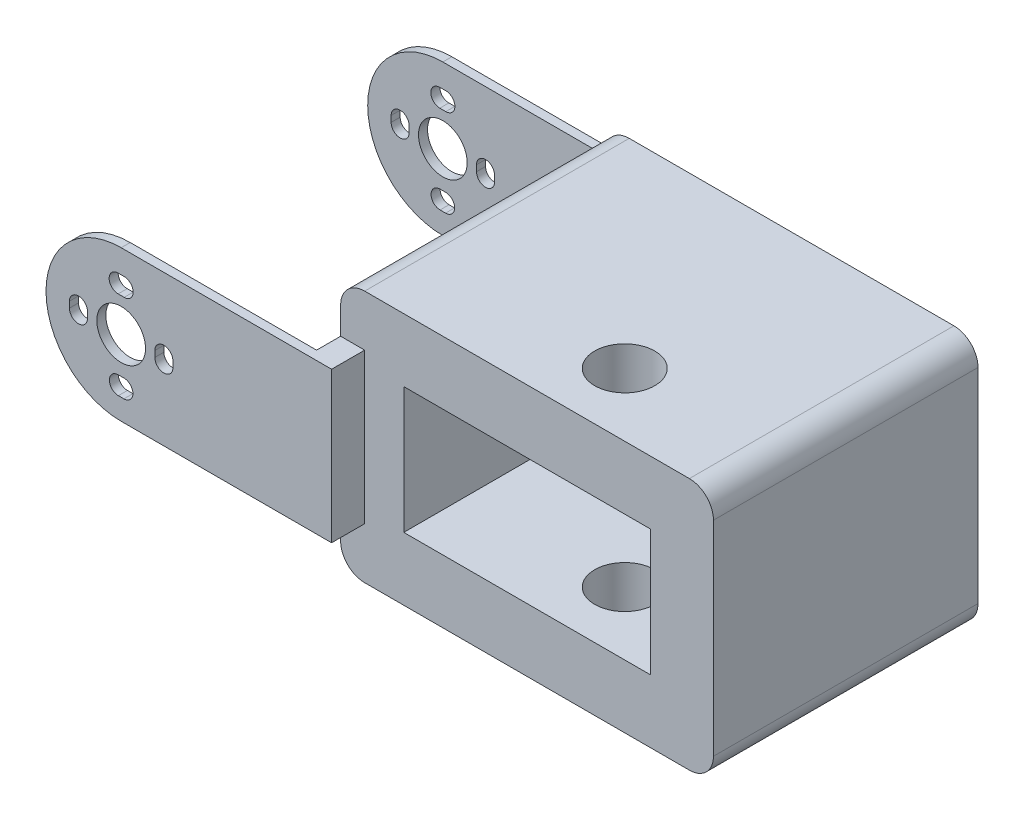
SolidWorks part; units mm, degrees
note: The reader was unsure of these and kept them because the rebuilt part matched: shared geometry of "Sketch3<8>", "Sketch3<11>", "草圖2<3>".
ref_plane "前基準面" through (0, 0, 0) normal (0, 0, 1) x (1, 0, 0)
ref_plane "上基準面" through (0, 0, 0) normal (0, 1, 0) x (1, 0, 0)
ref_plane "右基準面" through (0, 0, 0) normal (1, 0, 0) x (0, 0, -1)
sketch "Sketch1" plane through (0, 0, 0) normal (0, 0, 1) x (1, 0, 0)
  line L0 (-29.0958, -4.1361) -> (32.9042, -4.1361) construction
  line L1 (-18.5958, 6.3639) -> (22.4042, 6.3639)
  line L2 (-18.5958, 6.3639) -> (-18.5958, -14.6361)
  line L3 (-18.5958, -14.6361) -> (22.4042, -14.6361)
  line L4 (22.4042, 6.3639) -> (22.4042, -14.6361)
  line L5 (-29.0958, 16.8639) -> (32.9042, 16.8639)
  line L6 (-29.0958, 16.8639) -> (-29.0958, -25.1361)
  line L7 (-29.0958, -25.1361) -> (32.9042, -25.1361)
  line L8 (32.9042, 16.8639) -> (32.9042, -25.1361)
  line L9 (1.9042, 16.8639) -> (1.9042, -25.1361) construction
  line L10 (22.4042, -4.1361) -> (-18.5958, -4.1361) construction
  line L11 (1.9042, 6.3639) -> (1.9042, -14.6361) construction
  point P16 (1.9042, -4.1361)
  point P17 (1.9042, -4.1361)
  dimension "D1" = 21
  dimension "D2" = 41
  dimension "D3" = 62
  dimension "D4" = 42
extrude "Boss-Extrude1" add sketch "Sketch1" along normal blind 43
sketch "Sketch2" plane through (0, 0, 43) normal (0, 0, 1) x (1, 0, 0)
  line L0 (-18.5958, -4.1361) -> (-29.0958, -4.1361) construction
  line L1 (-25.0958, -4.1361) -> (-29.0958, -4.1361) construction
  line L3 (-29.0958, 16.8639) -> (-29.0958, -25.1361) construction
  line L4 (-18.5958, 6.3639) -> (-18.5958, -14.6361) construction
  line L5 (-29.0958, 8.3639) -> (-25.0958, 8.3639)
  line L6 (-29.0958, 8.3639) -> (-29.0958, -16.6361)
  line L7 (-29.0958, -16.6361) -> (-25.0958, -16.6361)
  line L8 (-25.0958, 8.3639) -> (-25.0958, -16.6361)
  dimension "D1" = 25
  dimension "D2" = 4
extrude "Boss-Extrude2" add sketch "Sketch2" along normal blind 4
sketch "Sketch3" plane through (0, 0, 47) normal (0, 0, 1) x (1, 0, 0)
  line L0 (-60.5958, 2.9639) -> (-59.5958, 2.9639) construction
  line L1 (-25.0958, 8.3639) -> (-60.0958, 8.3639)
  line L2 (-25.0958, 8.3639) -> (-25.0958, -16.6361)
  line L3 (-25.0958, -16.6361) -> (-60.0958, -16.6361)
  line L4 (-60.0958, 8.3639) -> (-60.0958, -16.6361)
  line L5 (-60.5958, 4.4639) -> (-59.5958, 4.4639)
  line L6 (-60.5958, 1.4639) -> (-59.5958, 1.4639)
  line L7 (-60.0958, 8.3639) -> (-60.0958, -16.6361) construction
  line L8 (-60.5559, -11.6762) -> (-59.6357, -11.6762) construction
  line L9 (-60.5559, -10.1762) -> (-59.6357, -10.1762)
  line L10 (-60.5559, -13.1762) -> (-59.6357, -13.1762)
  line L11 (-60.0958, -4.1361) -> (-72.5958, -4.1361) construction
  line L12 (-67.1958, -3.6361) -> (-67.1958, -4.6361) construction
  line L15 (-65.6958, -3.6361) -> (-65.6958, -4.6361)
  line L16 (-68.6958, -3.6361) -> (-68.6958, -4.6361)
  line L17 (-52.9958, -3.6361) -> (-52.9958, -4.6361) construction
  line L18 (-51.4958, -3.6361) -> (-51.4958, -4.6361)
  line L19 (-54.4958, -3.6361) -> (-54.4958, -4.6361)
  line L20 (-60.0958, -4.1361) -> (-25.0958, -4.1361) construction
  line L21 (-29.0958, 8.3639) -> (-29.0958, -16.6361) construction
  arc A0 (-60.0958, 8.3639) -> (-60.0958, -16.6361) centre (-60.0958, -4.1361) ccw
  circle A1 centre (-60.0958, -4.1361) radius 4.05
  arc A3 (-60.5958, 4.4639) -> (-60.5958, 1.4639) centre (-60.5958, 2.9639) ccw
  arc A4 (-59.5958, 1.4639) -> (-59.5958, 4.4639) centre (-59.5958, 2.9639) ccw
  arc A5 (-60.5559, -10.1762) -> (-60.5559, -13.1762) centre (-60.5559, -11.6762) ccw
  arc A6 (-59.6357, -13.1762) -> (-59.6357, -10.1762) centre (-59.6357, -11.6762) ccw
  arc A9 (-65.6958, -3.6361) -> (-68.6958, -3.6361) centre (-67.1958, -3.6361) ccw
  arc A10 (-68.6958, -4.6361) -> (-65.6958, -4.6361) centre (-67.1958, -4.6361) ccw
  arc A11 (-51.4958, -3.6361) -> (-54.4958, -3.6361) centre (-52.9958, -3.6361) ccw
  arc A12 (-54.4958, -4.6361) -> (-51.4958, -4.6361) centre (-52.9958, -4.6361) ccw
  point P9 (-60.0958, 2.9639)
  point P14 (-58.0958, 2.9639)
  point P15 (-62.0958, 2.9639)
  point P19 (-60.0958, -11.6762)
  point P25 (-67.1958, -4.1361)
  point P31 (-67.1958, -2.1361)
  point P32 (-67.1958, -6.1361)
  point P34 (-65.6958, -4.1361)
  point P37 (-52.9958, -4.1361)
  point P42 (-52.9958, -2.1361)
  point P43 (-52.9958, -6.1361)
  line M15 (-29.0958, 8.3639) -> (-29.0958, -16.6361)
  line M16 (-29.0958, -16.6361) -> (-25.0958, -16.6361)
  line M17 (-25.0958, -16.6361) -> (-25.0958, 8.3639)
  line M18 (-25.0958, 8.3639) -> (-29.0958, 8.3639)
  dimension "D2" = 4
  dimension "D10" = 5.6
  dimension "D9" = 4
  dimension "D3" = 3
  dimension "D4" = 5.6
  dimension "D5" = 25
  dimension "D6" = 6.0402
  dimension "D7" = 0
  dimension "D8" = 3
  dimension "D11" = 5.6
  dimension "D12" = 3
  dimension "D13" = 4
  dimension "D14" = 31
extrude "Boss-Extrude6" add sketch "Sketch3" along normal blind 1.5 contours A5 L9 L4 A1 L6 A3 L5 A0 L10 A10 L16 A9 L15 | A6 L10 L4 L3 L1 L5 A4 L6 A1 L9 A12 L19 A11 L18 M15 | M18 M15 M16 M17
extrude "Boss-Extrude7" add sketch "Sketch3<8>" against normal blind 53.5 contours A5 L9 L4 A1 L6 A3 L5 A0 L10 A10 L16 A9 L15 | A6 L10 L4 L3 L1 L5 A4 L6 A1 L9 A12 L19 A11 L18 M15 | M18 M15 M16 M17
sketch "Sketch3<8>" plane through (0, 0, 47) normal (0, 0, 1) x (1, 0, 0) same geometry as "Sketch3"
extrude "Cut-Extrude1" cut sketch "Sketch3<11>" against normal blind 52 contours A6 L10 L4 L3 L1 L5 A4 L6 A1 L9 A12 L19 A11 L18 M15 | A5 L9 L4 A1 L6 A3 L5 A0 L10 A10 L16 A9 L15
sketch "Sketch3<11>" plane through (0, 0, 47) normal (0, 0, 1) x (1, 0, 0) same geometry as "Sketch3"
sketch "草圖1" plane through (0, 16.8639, 0) normal (0, 1, 0) x (1, 0, 0)
  circle A1 centre (7.6538, -32.5004) radius 5
  dimension "D1" = 10
extrude "除料-伸長1" cut sketch "草圖1" against normal blind 42
sketch "草圖2" plane through (0, 0, 0) normal (0, 0, -1) x (-1, 0, 0)
  line L0 (-22.4042, -14.6361) -> (-22.4042, 6.3639)
  line L1 (-22.4042, 6.3639) -> (18.5958, 6.3639)
  line L2 (18.5958, 6.3639) -> (18.5958, -14.6361)
  line L3 (18.5958, -14.6361) -> (-22.4042, -14.6361)
  line L4 (18.5958, -4.1361) -> (-22.4042, -4.1361) construction
  line L6 (29.0958, 16.8639) -> (29.0958, -25.1361)
  line L7 (29.0958, -25.1361) -> (-32.9042, -25.1361) construction
  line L8 (29.0958, -16.6361) -> (29.0958, -25.1361) construction
  line L9 (29.0958, -25.1361) -> (-32.9042, -25.1361)
  line L10 (-32.9042, -25.1361) -> (-32.9042, 16.8639)
  line L11 (-32.9042, 16.8639) -> (29.0958, 16.8639) construction
  line L12 (-32.9042, -25.1361) -> (-32.9042, 16.8639) construction
  line L13 (-32.9042, 16.8639) -> (29.0958, 16.8639)
  circle A0 centre (-12.4042, -4.1361) radius 7
  line M14 (18.5958, 6.3639) -> (18.5958, -14.6361)
  line M15 (18.5958, -14.6361) -> (-22.4042, -14.6361)
  line M16 (-22.4042, -14.6361) -> (-22.4042, 6.3639)
  line M17 (-22.4042, 6.3639) -> (18.5958, 6.3639)
  dimension "D1" = 14
  dimension "D2" = 10
extrude "填料-伸長1" add sketch "草圖2" against normal blind 1 contours L4 L0 A0 M14 M17 | L2 L4 A0 M16 M15
extrude "填料-伸長2" add sketch "草圖2<3>" along normal blind 1
sketch "草圖2<3>" plane through (0, 0, 0) normal (0, 0, -1) x (-1, 0, 0) same geometry as "草圖2"
fillet "圓角1" radius 4 1 edges at (32.9042, -25.1361, 21)
fillet "圓角2" radius 4 1 edges at (-29.0958, -25.1361, 21)
fillet "圓角3" radius 4 1 edges at (32.9042, 16.8639, 21)
fillet "圓角4" radius 4 1 edges at (-29.0958, 16.8639, 21)
